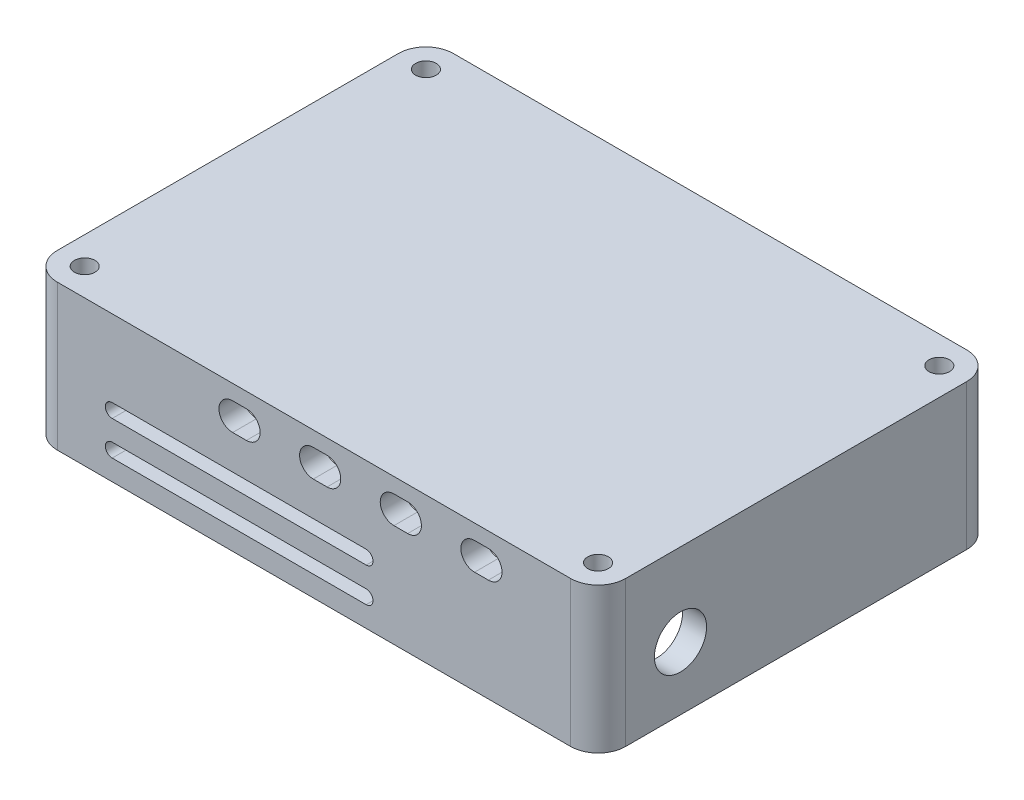
SolidWorks part; units mm, degrees
material "ABS"
ref_plane "Front Plane" through (0, 0, 0) normal (0, 0, 1) x (1, 0, 0)
ref_plane "Top Plane" through (0, 0, 0) normal (0, 1, 0) x (1, 0, 0)
ref_plane "Right Plane" through (0, 0, 0) normal (1, 0, 0) x (0, 0, -1)
sketch "Sketch1" plane through (0, 0, 0) normal (0, 1, 0) x (1, 0, 0)
  line L1 (-109.9297, 31.1354) -> (-27.1297, 31.1354)
  line L2 (-109.9297, 31.1354) -> (-109.9297, -26.5646)
  line L3 (-109.9297, -26.5646) -> (-27.1297, -26.5646)
  line L4 (-27.1297, 31.1354) -> (-27.1297, -26.5646)
  line L5 (-109.9297, 31.1354) -> (-27.1297, -26.5646) construction
  line L6 (-109.9297, -26.5646) -> (-27.1297, 31.1354) construction
  point P0 (-68.5297, 2.2854)
extrude "Boss-Extrude1" add sketch "Sketch1" along normal blind 21.2
sketch "Sketch2" plane through (0, 0, 0) normal (0, -1, 0) x (1, 0, 0)
  line L0 (-27.1297, 26.5646) -> (-27.1297, -31.1354) construction
  line L1 (-109.9297, -31.1354) -> (-109.9297, 26.5646) construction
  circle A0 centre (-105.9297, 22.5741) radius 1.5
  circle A1 centre (-31.1297, 22.5741) radius 1.5
  circle A2 centre (-105.9297, -27.1448) radius 1.5
  circle A3 centre (-31.1297, -27.1448) radius 1.5
  dimension "D1" = 4
  dimension "D2" = 4
  dimension "D3" = 4
  dimension "D4" = 4
extrude "Cut-Extrude1" cut sketch "Sketch2" against normal blind 22
sketch "Sketch3" plane through (0, 0, 0) normal (0, -1, 0) x (1, 0, 0)
  line L1 (-101.9693, 23.0646) -> (-35.09, 23.0646)
  line L2 (-106.4297, 18.6072) -> (-106.4297, -23.175)
  line L3 (-101.9693, -27.6354) -> (-35.09, -27.6354)
  line L4 (-30.6297, 18.6043) -> (-30.6297, -23.175)
  line L5 (-103.3343, 24.0646) -> (-33.7237, 24.0646)
  line L6 (-29.6297, 19.9706) -> (-29.6297, -24.5413)
  line L10 (-103.3356, -28.6354) -> (-33.7237, -28.6354)
  line L11 (-107.4297, 19.9733) -> (-107.4297, -24.5413)
  line L13 (-106.4297, -23.175) -> (-106.4297, 18.6043) construction
  arc A0 (-106.4297, 18.6072) -> (-101.9693, 23.0646) centre (-105.9395, 22.577) ccw
  arc A1 (-35.09, 23.0646) -> (-30.6297, 18.6043) centre (-31.1202, 22.5741) ccw
  arc A2 (-30.6297, -23.175) -> (-35.09, -27.6354) centre (-31.1202, -27.1448) ccw
  arc A3 (-101.9693, -27.6354) -> (-106.4297, -23.175) centre (-105.9391, -27.1448) ccw
  arc A4 (-33.7237, 24.0646) -> (-29.6297, 19.9706) centre (-31.1202, 22.5741) ccw
  arc A5 (-29.6297, -24.5413) -> (-33.7237, -28.6354) centre (-31.1202, -27.1448) ccw
  arc A6 (-103.3356, -28.6354) -> (-107.4297, -24.5413) centre (-105.9391, -27.1448) ccw
  arc A7 (-107.4297, 19.9733) -> (-103.3343, 24.0646) centre (-105.9395, 22.577) ccw
  arc A8 (-30.6297, -23.175) -> (-35.09, -27.6354) centre (-31.1202, -27.1448) ccw construction
  point P0 (-67.3297, -2.2854)
  dimension "D5" = 1
extrude "Cut-Extrude2" cut sketch "Sketch3" against normal blind 20 contours A0 L1 A1 L4 A2 L3 A3 L2
fillet "Fillet3" radius 4 4 edges at (-27.1297, 10.6, 26.5646) (-109.9297, 10.6, 26.5646) (-109.9297, 10.6, -31.1354) (-27.1297, 10.6, -31.1354)
extrude "Boss-Extrude3" add sketch "Sketch3<8>" along normal blind 1
sketch "Sketch3<8>" plane through (0, 0, 0) normal (0, -1, 0) x (1, 0, 0) same geometry as "Sketch3"
sketch "Sketch7" plane through (0, 0, -31.1354) normal (0, 0, -1) x (-1, 0, 0)
  line L0 (97.9297, 3) -> (60.9297, 3)
  line L1 (97.9297, 5) -> (60.9297, 5)
  line L2 (97.9297, 3) -> (97.9297, 5) construction
  line L3 (60.9297, 3) -> (60.9297, 5) construction
  line L4 (109.9297, 21.2) -> (109.9297, 0) construction
  line L5 (31.1297, 0) -> (105.9297, 0) construction
  line L6 (97.9297, 8) -> (60.9297, 8)
  line L7 (97.9297, 10) -> (60.9297, 10)
  line L8 (97.9297, 8) -> (97.9297, 10) construction
  line L9 (60.9297, 8) -> (60.9297, 10) construction
  arc A0 (97.9297, 3) -> (97.9297, 5) centre (97.9297, 4) ccw
  arc A1 (60.9297, 5) -> (60.9297, 3) centre (60.9297, 4) ccw
  arc A2 (97.9297, 8) -> (97.9297, 10) centre (97.9297, 9) ccw
  arc A3 (60.9297, 10) -> (60.9297, 8) centre (60.9297, 9) ccw
  dimension "D2" = 37
  dimension "D3" = 12
  dimension "D1" = 2
  dimension "D4" = 3
  dimension "D5" = 2
extrude "Cut-Extrude6" cut sketch "Sketch7" against normal through all contours L7 A3 L6 A2 | L1 A1 L0 A0 region at (-79.4297, 4, -31.1354) region at (-79.4297, 9, -31.1354)
sketch "Sketch8" plane through (-109.9297, 0, 0) normal (-1, 0, 0) x (0, 0, 1)
  line L0 (26.5646, 21.2) -> (26.5646, 0) construction
  line L1 (-27.1354, 21.2) -> (22.5646, 21.2) construction
  circle A0 centre (14.5646, 9.2) radius 3.8
  dimension "D1" = 12
  dimension "D2" = 12
extrude "Cut-Extrude7" cut sketch "Sketch8" against normal through all
sketch "Sketch10" plane through (0, 0, 26.5646) normal (0, 0, 1) x (1, 0, 0)
  line L2 (-43.1297, 17) -> (-45.1297, 17) construction
  line L3 (-43.1297, 15) -> (-45.1297, 15)
  line L4 (-43.1297, 19) -> (-45.1297, 19)
  line L5 (-33.7237, -1) -> (-103.3343, -1) construction
  line L6 (-27.1297, 21.2) -> (-27.1297, 0) construction
  line L7 (-54.8797, 17) -> (-56.8797, 17) construction
  line L8 (-54.8797, 15) -> (-56.8797, 15)
  line L9 (-54.8797, 19) -> (-56.8797, 19)
  line L10 (-66.6297, 17) -> (-68.6297, 17) construction
  line L11 (-66.6297, 15) -> (-68.6297, 15)
  line L12 (-66.6297, 19) -> (-68.6297, 19)
  line L13 (-78.3797, 17) -> (-80.3797, 17) construction
  line L14 (-78.3797, 15) -> (-80.3797, 15)
  line L15 (-78.3797, 19) -> (-80.3797, 19)
  arc A0 (-43.1297, 15) -> (-43.1297, 19) centre (-43.1297, 17) ccw
  arc A1 (-54.8797, 15) -> (-54.8797, 19) centre (-54.8797, 17) ccw
  arc A2 (-56.8797, 19) -> (-56.8797, 15) centre (-56.8797, 17) ccw
  arc A3 (-66.6297, 15) -> (-66.6297, 19) centre (-66.6297, 17) ccw
  arc A4 (-45.1297, 19) -> (-45.1297, 15) centre (-45.1297, 17) ccw
  arc A5 (-68.6297, 19) -> (-68.6297, 15) centre (-68.6297, 17) ccw
  arc A6 (-78.3797, 15) -> (-78.3797, 19) centre (-78.3797, 17) ccw
  arc A7 (-80.3797, 19) -> (-80.3797, 15) centre (-80.3797, 17) ccw
  point P2 (-44.1297, 17)
  point P10 (-55.8797, 17)
  point P23 (-67.6297, 17)
  point P30 (-79.3797, 17)
  dimension "D1" = 18
  dimension "D3" = 4
  dimension "D2" = 17
extrude "Cut-Extrude8" cut sketch "Sketch10" against normal blind 10
